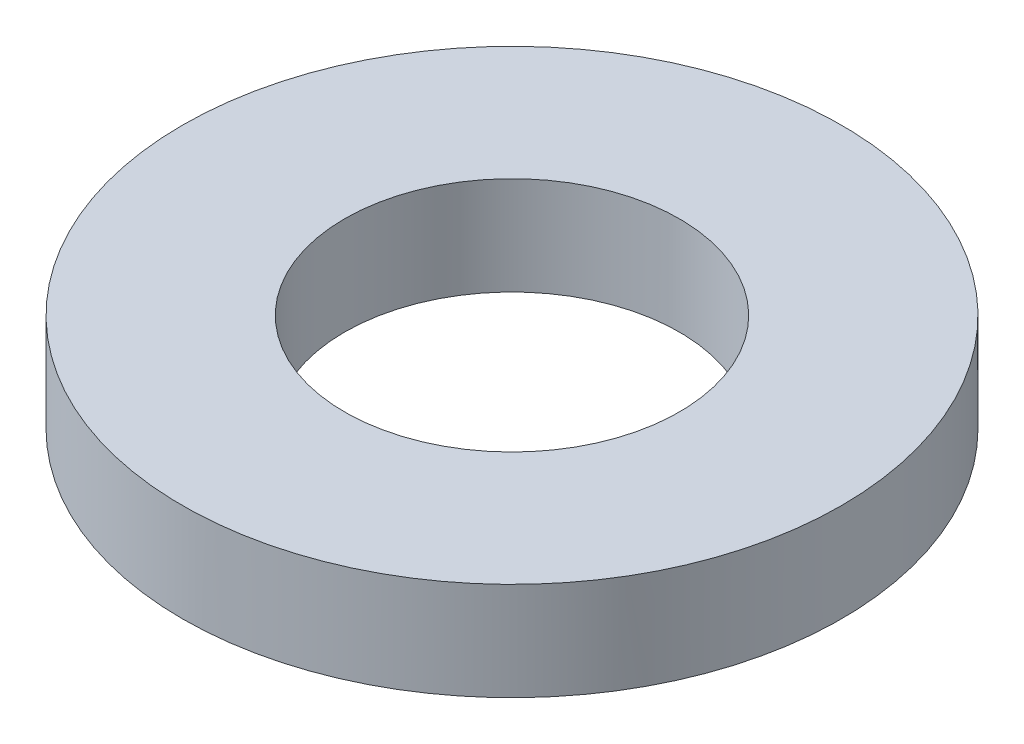
SolidWorks part; units mm, degrees
ref_plane "Front Plane" through (0, 0, 0) normal (0, 0, 1) x (1, 0, 0)
ref_plane "Top Plane" through (0, 0, 0) normal (0, 1, 0) x (1, 0, 0)
ref_plane "Right Plane" through (0, 0, 0) normal (1, 0, 0) x (0, 0, -1)
sketch "Sketch1" plane through (0, 0, 0) normal (0, 1, 0) x (1, 0, 0)
  circle A0 centre (0, 0) radius 6.35
  arc A4 (-4.0962, 4.8522) -> (1.8698, -6.0685) centre (0, 0) ccw construction
  circle A5 centre (0, 0) radius 3.2258
  circle A6 centre (0, 0) radius 3.2258
  dimension "D1" = 0.0508
extrude "Boss-Extrude1" add sketch "Sketch1" along normal up to surface (1.8914 mm away)
